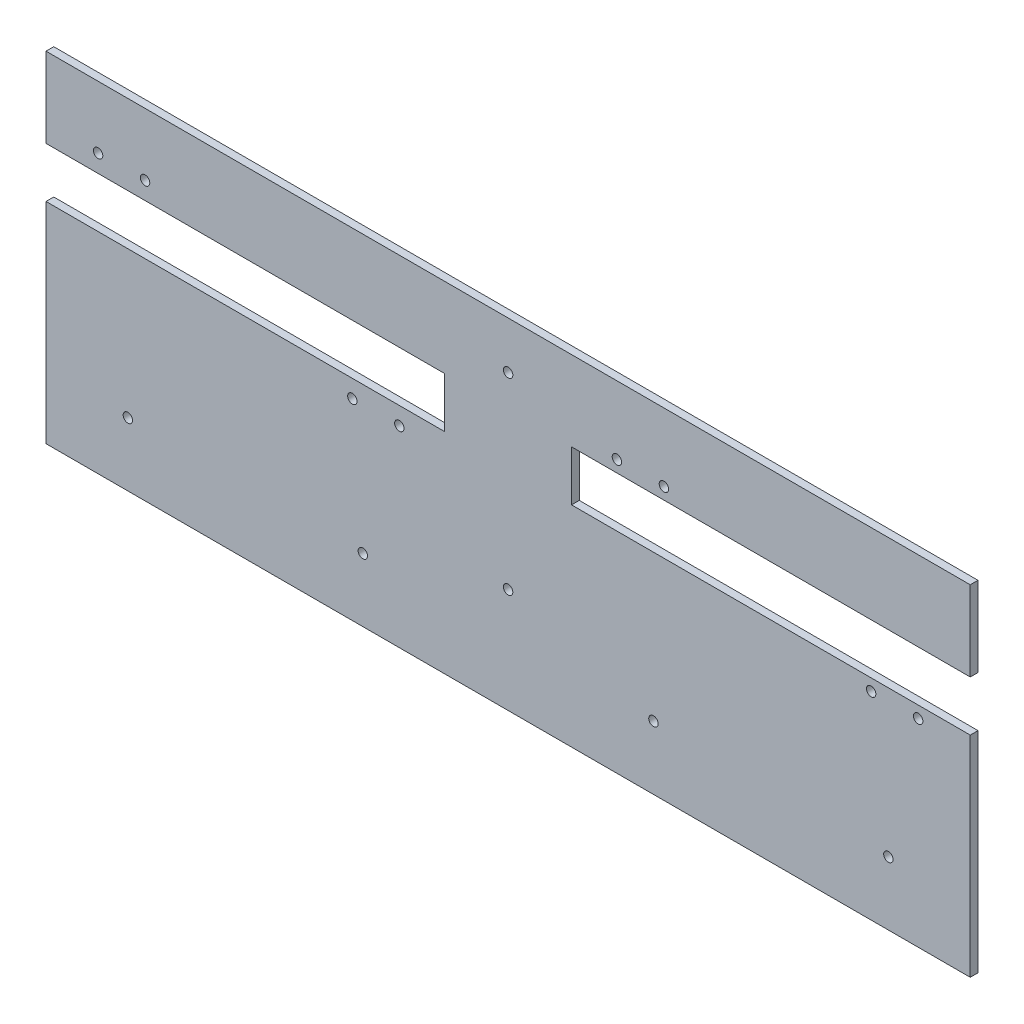
SolidWorks part; units mm, degrees
material "Balsa"
ref_plane "Front Plane" through (0, 0, 0) normal (0, 0, 1) x (1, 0, 0)
ref_plane "Top Plane" through (0, 0, 0) normal (0, 1, 0) x (1, 0, 0)
ref_plane "Right Plane" through (0, 0, 0) normal (1, 0, 0) x (0, 0, -1)
sketch "Sketch1" plane through (0, 0, 0) normal (0, 0, 1) x (1, 0, 0)
  line L1 (223.7, -24.5) -> (-169.7, -24.5)
  line L2 (223.7, -24.5) -> (223.7, 120.2)
  line L3 (223.7, 120.2) -> (-169.7, 120.2)
  line L4 (-169.7, -24.5) -> (-169.7, 120.2)
  line L5 (223.7, -24.5) -> (-169.7, 120.2) construction
  line L6 (223.7, 120.2) -> (-169.7, -24.5) construction
  line L7 (227, -24.5) -> (223.7, -24.5) construction
  line L10 (223.7, 144.1231) -> (223.7, -24.5) construction
  line L11 (-169.7, -24.5) -> (-169.7, 144.1269) construction
  line L12 (-169.7, 120.2) -> (223.7, 120.2) construction
  point P4 (27, 60.5912)
extrude "Boss-Extrude1" add sketch "Sketch1" along normal up to surface (3.3 mm away)
sketch "Sketch2" plane through (0, 0, 0) normal (0, 0, -1) x (-1, 0, 0)
  line L0 (-223.7, 120.2) -> (169.7, 120.2) construction
  line L1 (0, 0) -> (-54, 0)
  line L2 (0, 0) -> (0, 120.2)
  line L3 (0, 120.2) -> (-54, 120.2)
  line L4 (-54, 0) -> (-54, 120.2)
  line L5 (0, 0) -> (-54, 120.2) construction
  line L6 (0, 120.2) -> (-54, 0) construction
  line L7 (-54, 262.7) -> (-54, 0) construction
  line L8 (-27, 0) -> (-27, 120.2) construction
  line L9 (169.7, 120.2) -> (169.7, -24.5) construction
  line L10 (-223.7, 29.5) -> (-54, 29.5)
  line L11 (-223.7, 29.5) -> (-223.7, -24.5)
  line L12 (-223.7, -24.5) -> (-54, -24.5)
  line L13 (-54, 29.5) -> (-54, -24.5)
  line L14 (-223.7, 29.5) -> (-54, -24.5) construction
  line L15 (-223.7, -24.5) -> (-54, 29.5) construction
  line L16 (169.7, 29.5) -> (0, 29.5)
  line L17 (169.7, 29.5) -> (169.7, -24.5)
  line L18 (169.7, -24.5) -> (0, -24.5)
  line L19 (0, 29.5) -> (0, -24.5)
  line L20 (169.7, 29.5) -> (0, -24.5) construction
  line L21 (169.7, -24.5) -> (0, 29.5) construction
  line L22 (-223.7, 2.5) -> (169.7, 2.5) construction
  line L23 (-138.85, -24.5) -> (-138.85, 29.5) construction
  circle A0 centre (-27, 20.1) radius 2
  circle A1 centre (-27, 100.1) radius 2
  circle A2 centre (-188.85, 2.5) radius 2
  circle A3 centre (-88.85, 2.5) radius 2
  circle A4 centre (34.85, 2.5) radius 2
  circle A5 centre (134.85, 2.5) radius 2
  point P4 (-27, 60.1)
  point P20 (-138.85, 2.5)
  point P27 (84.85, 2.5)
  dimension "D1" = 4
  dimension "D2" = 4
  dimension "D3" = 40
  dimension "D4" = 40
  dimension "D5" = 4
  dimension "D6" = 50
extrude "Cut-Extrude1" cut sketch "Sketch2" against normal blind 4 contours A1 | A0 | A2 | A3 | A5 | A4
sketch "Sketch3" plane through (0, 0, 0) normal (0, 0, -1) x (-1, 0, 0)
  line L0 (169.7, 120.2) -> (169.7, -24.5) construction
  line L1 (169.7, 64.8) -> (-223.7, 64.8)
  line L2 (169.7, 64.8) -> (169.7, 86.2)
  line L3 (169.7, 86.2) -> (-223.7, 86.2)
  line L4 (-223.7, 64.8) -> (-223.7, 86.2)
  line L5 (169.7, 64.8) -> (-223.7, 86.2) construction
  line L6 (169.7, 86.2) -> (-223.7, 64.8) construction
  line L7 (-223.7, -24.5) -> (-223.7, 120.2) construction
  line L8 (35.8344, 64.8) -> (9.0983, 64.8) construction
  line L9 (142.922, 86.2) -> (163.7817, 86.2) construction
  line L10 (0, 64.8) -> (0, 86.2)
  line L11 (-54, 64.8) -> (-54, 86.2)
  line L12 (-54, 262.7) -> (-54, 0) construction
  line L13 (0, 262.7) -> (0, 0) construction
  line L14 (0, 262.7) -> (0, 0) construction
  point P4 (-27, 75.5)
  line M7 (-223.7, 120.2) -> (-223.7, -24.5)
  line M9 (169.7, -24.5) -> (169.7, 120.2)
extrude "Cut-Extrude2" cut sketch "Sketch3" against normal blind 6 contours L10 L1 L3 M9 | L1 L11 L3 M7 region at (-84.85, 75.5, 0) region at (138.85, 75.5, 0)
sketch "Sketch4" plane through (0, 0, 3.3) normal (0, 0, 1) x (1, 0, 0)
  circle A0 centre (93.3034, 91.2) radius 2
  circle A1 centre (73.3034, 91.2) radius 2
  circle A2 centre (181.5258, 59.8) radius 2
  circle A3 centre (201.5258, 59.8) radius 2
  circle A4 centre (-127.5258, 93.7) radius 2
  circle A5 centre (-147.5258, 93.7) radius 2
  circle A6 centre (-19.3034, 57.3) radius 2
  circle A7 centre (-39.3034, 57.3) radius 2
  circle A8 centre (-39.3034, 57.3) radius 2 construction
  circle A9 centre (-19.3034, 57.3) radius 2 construction
  circle A10 centre (-127.5258, 93.7) radius 2 construction
  circle A11 centre (-147.5258, 93.7) radius 2 construction
  circle A12 centre (181.5258, 59.8) radius 2 construction
  circle A13 centre (93.3034, 91.2) radius 2 construction
  circle A14 centre (73.3034, 91.2) radius 2 construction
  circle A15 centre (201.5258, 59.8) radius 2 construction
extrude "Cut-Extrude3" cut sketch "Sketch4" against normal through all
